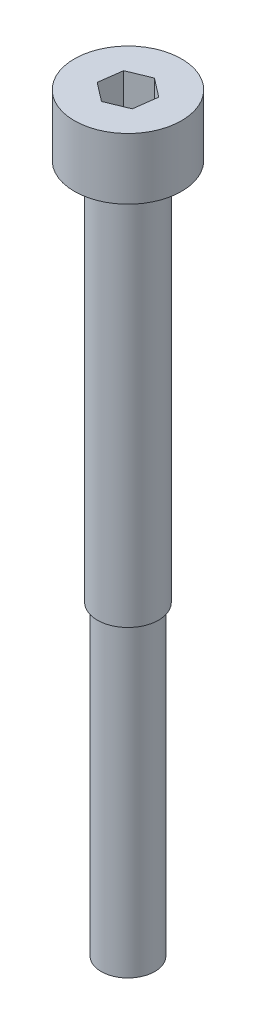
SolidWorks part; units mm, degrees
ref_plane "前视基准面" through (0, 0, 0) normal (0, 0, 1) x (1, 0, 0)
ref_plane "上视基准面" through (0, 0, 0) normal (0, 1, 0) x (1, 0, 0)
ref_plane "右视基准面" through (0, 0, 0) normal (1, 0, 0) x (0, 0, -1)
sketch "草图1" plane through (0, 0, 0) normal (0, 1, 0) x (1, 0, 0)
  circle A0 centre (0, 0) radius 2
  circle A1 centre (0, 0) radius 1.75
  dimension "D1" = 4
  dimension "D2" = 3.5
extrude "凸台-拉伸1" add sketch "草图1" along normal blind 25 contours A1 | A0 A1 region at (-1.9434, 0, 0) region at (0, 0, 0)
extrude "凸台-拉伸2" add sketch "草图1<3>" against normal blind 20 contours A1 region at (0, 0, 0)
sketch "草图1<3>" plane through (0, 0, 0) normal (0, 1, 0) x (1, 0, 0) same geometry as "草图1"
sketch "草图2" plane through (0, 25, 0) normal (0, 1, 0) x (1, 0, 0)
  circle A0 centre (0, 0) radius 3.5
  dimension "D1" = 7
extrude "凸台-拉伸3" add sketch "草图2" along normal blind 4
sketch "草图3" plane through (0, 29, 0) normal (0, 1, 0) x (1, 0, 0)
  line L1 (1.2204, -0.9392) -> (1.4236, 0.5873)
  line L2 (1.4236, 0.5873) -> (0.2032, 1.5265)
  line L3 (0.2032, 1.5265) -> (-1.2204, 0.9392)
  line L4 (-1.2204, 0.9392) -> (-1.4236, -0.5873)
  line L5 (-1.4236, -0.5873) -> (-0.2032, -1.5265)
  line L6 (-0.2032, -1.5265) -> (1.2204, -0.9392)
  circle A0 centre (0, 0) radius 1.3337 construction
  dimension "D1" = 3.08
extrude "切除-拉伸1" cut sketch "草图3" against normal blind 3
